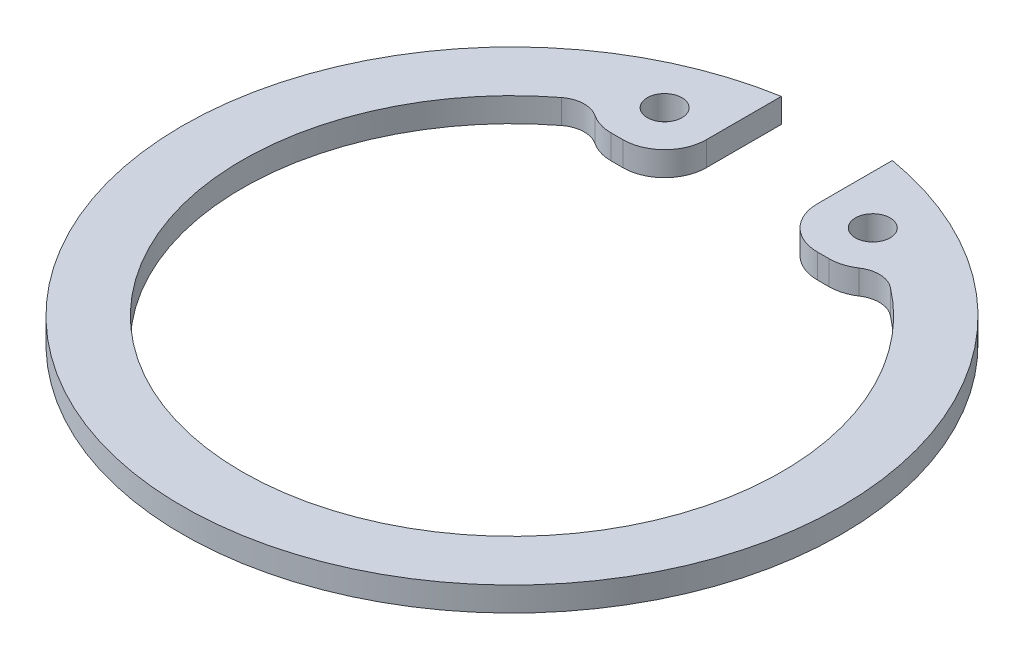
SolidWorks part; units mm, degrees
ref_plane "Front Plane" through (0, 0, 0) normal (0, 0, 1) x (1, 0, 0)
ref_plane "Top Plane" through (0, 0, 0) normal (0, 1, 0) x (1, 0, 0)
ref_plane "Right Plane" through (0, 0, 0) normal (1, 0, 0) x (0, 0, -1)
sketch "Sketch1" plane through (0, 0, 0) normal (0, 1, 0) x (1, 0, 0)
  line L0 (-4, 23.4107) -> (-4, 19.0342)
  line L1 (4, 23.4107) -> (4, 19.0342)
  line L2 (0, -0.9625) -> (0, 0.9625) construction
  line L3 (-4, 19.0342) -> (-4, 15)
  line L4 (-4, 15) -> (-9, 15)
  line L5 (-9, 15) -> (-9, 17.2425)
  line L6 (-0.9625, 0) -> (0.9625, 0) construction
  line L7 (4, 19.0342) -> (4, 15)
  line L8 (4, 15) -> (9, 15)
  line L9 (9, 15) -> (9, 17.2425)
  arc A0 (-4, 23.4107) -> (4, 23.4107) centre (0, 0) ccw
  arc A1 (-9, 17.2425) -> (9, 17.2425) centre (0, 0) ccw
  circle A2 centre (0, 0) radius 15.8 construction
  dimension "D1" = 47.5
  dimension "D2" = 38.9
  dimension "D3" = 31.6
  dimension "D4" = 4
  dimension "D5" = 4
  dimension "D6" = 15
  dimension "D7" = 5
  dimension "D8" = 5
extrude "Boss-Extrude1" add sketch "Sketch1" along normal blind 1.75
fillet "Fillet2" radius 2 2 edges at (9, 0.875, -17.2425) (-9, 0.875, -17.2425)
fillet "Fillet3" radius 3 4 edges at (4, 0.875, -15) (-4, 0.875, -15) (-9, 0.875, -15) (9, 0.875, -15)
sketch "Sketch2" plane through (0, 1.75, 0) normal (0, 1, 0) x (1, 0, 0)
  line L0 (0, -0.9625) -> (0, 0.9625) construction
  line L1 (-0.9625, 0) -> (0.9625, 0) construction
  circle A0 centre (-7.5, 18.5) radius 1.25
  circle A1 centre (7.5, 18.5) radius 1.25
  dimension "D1" = 2.5
  dimension "D2" = 2.5
  dimension "D4" = 7.5
  dimension "D5" = 18.5
  dimension "D6" = 18.5
  dimension "D3" = 7.5
extrude "Cut-Extrude1" cut sketch "Sketch2" against normal blind 1.75
